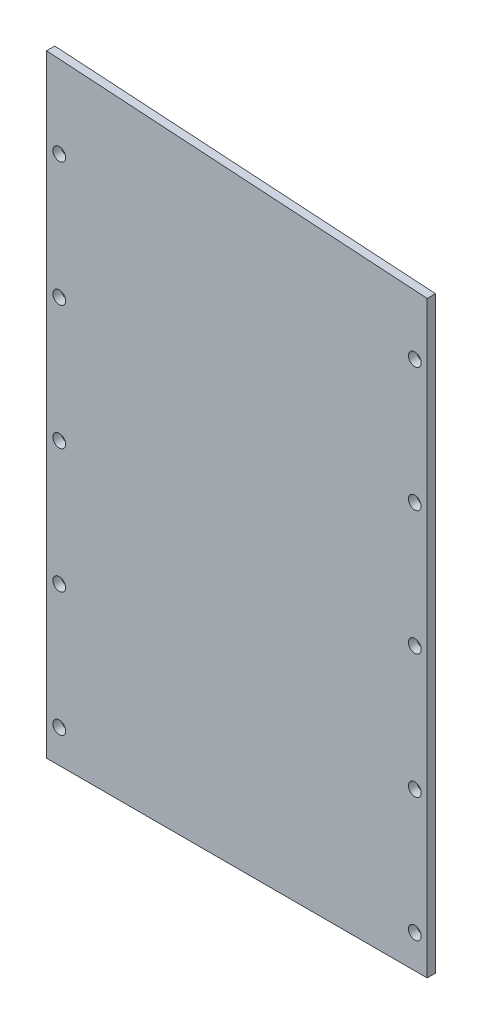
SolidWorks part; units mm, degrees
material "Acrylic (Medium-high impact)"
ref_plane "Front" through (0, 0, 0) normal (0, 0, 1) x (1, 0, 0)
ref_plane "Top" through (0, 0, 0) normal (0, 1, 0) x (1, 0, 0)
ref_plane "Right" through (0, 0, 0) normal (1, 0, 0) x (0, 0, -1)
sketch "Sketch1" plane through (0, 0, 0) normal (0, 0, 1) x (1, 0, 0)
  line L0 (-975.4136, 6405.0254) -> (-829.3636, 6405.0254) construction
  line L1 (-829.3636, 6406.6129) -> (-975.4136, 6406.6129)
  line L2 (-829.3636, 6406.6129) -> (-829.3636, 6632.3896)
  line L3 (-829.3636, 6632.3896) -> (-975.4136, 6641.6463)
  line L4 (-975.4136, 6406.6129) -> (-975.4136, 6641.6463)
  line L5 (-829.3636, 6405.0254) -> (-829.3636, 6281.2004) construction
  line L6 (-975.4136, 6281.2004) -> (-975.4136, 6405.0254) construction
  dimension "D1" = 1.5875
  dimension "D2" = 3.175
  dimension "D3" = 3.175
extrude "Boss-Extrude1" add sketch "Sketch1" along normal blind 3.175
hole_wizard "#8 Clearance Hole1" positions "Sketch2" profile "Sketch3" hole size "#8" standard "ANSI Inch" end condition up to next
sketch "Sketch2" plane through (0, 0, 3.175) normal (0, 0, 1) x (1, 0, 0)
  point P0 (-970.5241, 6609.8129)
  point P3 (-970.5241, 6562.1879)
  point P6 (-970.5241, 6514.5629)
  point P9 (-970.5241, 6466.9379)
  point P12 (-970.5241, 6419.3129)
  point P15 (-834.1261, 6419.3129)
  point P18 (-834.1261, 6466.9379)
  point P21 (-834.1261, 6514.5629)
  point P24 (-834.1261, 6562.1879)
  point P27 (-834.1261, 6609.8129)
sketch "Sketch3" plane through (-970.5241, 6609.8129, 3.175) normal (1, 0, 0) x (0, -1, 0)
  line L0 (0, 0) -> (0, 3.175)
  line L1 (0, 3.175) -> (2.4574, 3.175)
  line L2 (2.4574, 3.175) -> (2.4574, 0)
  line L5 (2.4574, 0) -> (0, 0)
  line L11 (0, -6.35) -> (0, 107.95) construction
  dimension "Thru Hole Dia." = 4.9149
  dimension "Thru Hole Depth" = 3.175
